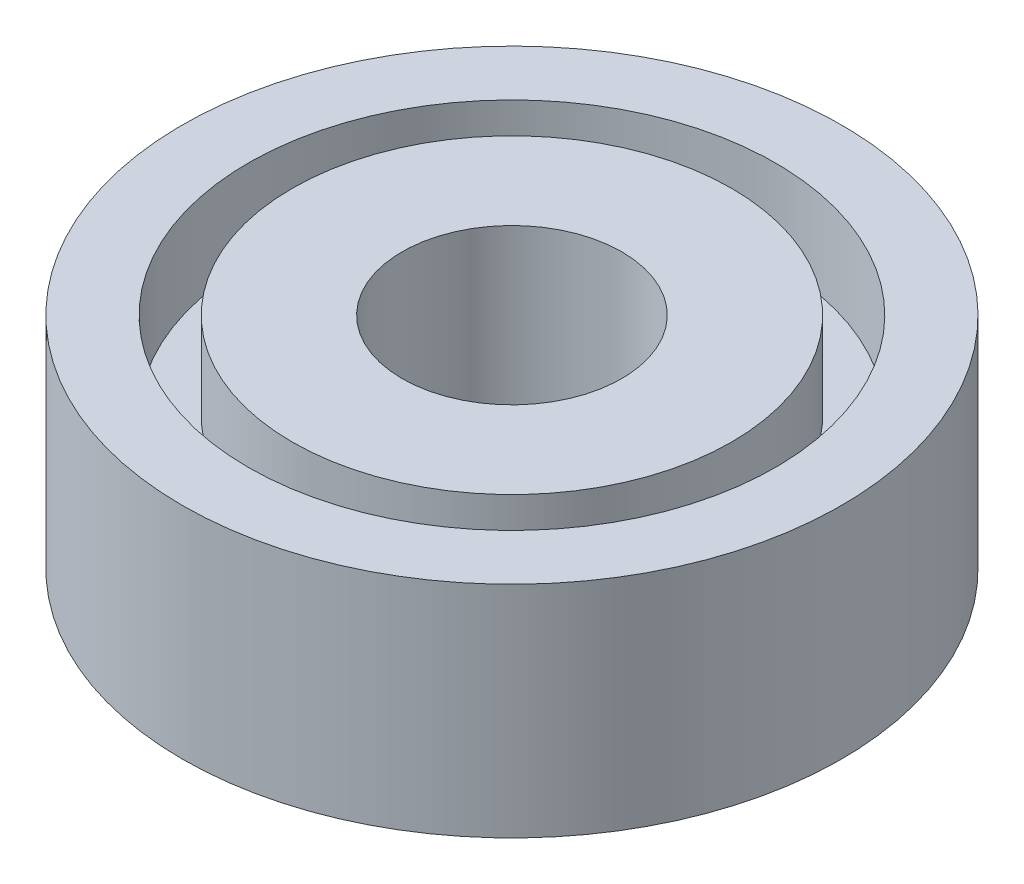
SolidWorks part; units mm, degrees
ref_plane "前视基准面" through (0, 0, 0) normal (0, 0, 1) x (1, 0, 0)
ref_plane "上视基准面" through (0, 0, 0) normal (0, 1, 0) x (1, 0, 0)
ref_plane "右视基准面" through (0, 0, 0) normal (1, 0, 0) x (0, 0, -1)
other "Configuration Table"
sketch "草图1" plane through (0, 0, 0) normal (0, 1, 0) x (1, 0, 0)
  circle A0 centre (0, 0) radius 1.5
  circle A1 centre (0, 0) radius 0.5
  circle A2 centre (0, 0) radius 1
  dimension "D1" = 1
  dimension "D2" = 3
  dimension "D3" = 2
extrude "凸台-拉伸1" add sketch "草图1" along normal blind 1 contours A1 | A0 region at (0, 0, 0)
extrude "切除-拉伸-薄壁1" cut sketch "草图1<3>" along normal blind 0.4 thin contours A2 thin type one direction wall 0.2
sketch "草图1<3>" plane through (0, 0, 0) normal (0, 1, 0) x (1, 0, 0) same geometry as "草图1"
extrude "切除-拉伸-薄壁2" cut sketch "草图1<4>" against normal blind 0.4 from surface thin contours A2 starting at face at (0, 1, 1.5) thin type one direction wall 0.2
sketch "草图1<4>" plane through (0, 0, 0) normal (0, 1, 0) x (1, 0, 0) same geometry as "草图1"
